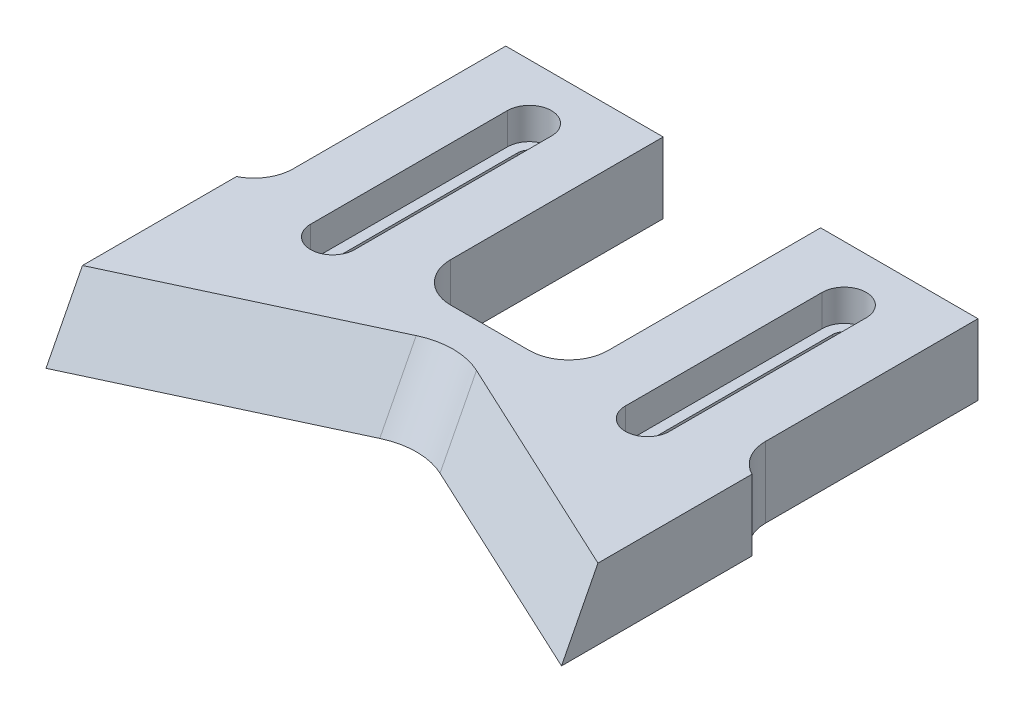
SolidWorks part; units mm, degrees
material "POM Acetal Copolymer"
ref_plane "Front Plane" through (0, 0, 0) normal (0, 0, 1) x (1, 0, 0)
ref_plane "Top Plane" through (0, 0, 0) normal (0, 1, 0) x (1, 0, 0)
ref_plane "Right Plane" through (0, 0, 0) normal (1, 0, 0) x (0, 0, -1)
sketch "Sketch1" plane through (0, 0, 0) normal (0, 1, 0) x (1, 0, 0)
  line L0 (0, 0) -> (0, 58)
  line L1 (0, 58) -> (75.5, 58)
  line L2 (75.5, 58) -> (75.5, 0)
  line L3 (75.5, 0) -> (37.75, 17.6031)
  line L4 (37.75, 17.6031) -> (0, 0)
  dimension "D1" = 58
  dimension "D2" = 65
  dimension "D3" = 75.5
extrude "Boss-Extrude1" add sketch "Sketch1" along normal blind 9
sketch "Sketch4" plane through (0, 9, 0) normal (0, 1, 0) x (1, 0, 0)
  line L0 (17.75, 51) -> (17.75, 26) construction
  line L1 (19.25, 51) -> (19.25, 26)
  line L2 (16.25, 51) -> (16.25, 26)
  line L3 (57.75, 51) -> (57.75, 26) construction
  line L4 (59.25, 51) -> (59.25, 26)
  line L5 (56.25, 51) -> (56.25, 26)
  line L6 (75.5, 58) -> (0, 58) construction
  line L9 (75.5, 58) -> (0, 58) construction
  arc A0 (19.25, 51) -> (16.25, 51) centre (17.75, 51) ccw
  arc A1 (16.25, 26) -> (19.25, 26) centre (17.75, 26) ccw
  arc A2 (59.25, 51) -> (56.25, 51) centre (57.75, 51) ccw
  arc A3 (56.25, 26) -> (59.25, 26) centre (57.75, 26) ccw
  point P2 (17.75, 38.5)
  point P7 (57.75, 38.5)
  point P14 (37.75, 58)
  dimension "D1" = 3
  dimension "D2" = 3
  dimension "D3" = 40
  dimension "D4" = 20
  dimension "D5" = 25
  dimension "D6" = 7
extrude "Cut-Extrude2" cut sketch "Sketch4" against normal up to next
sketch "Sketch5" plane through (0, 9, 0) normal (0, 1, 0) x (1, 0, 0)
  line L0 (75.5, 58) -> (0, 58) construction
  line L1 (27.75, 58) -> (47.75, 58)
  line L2 (27.75, 58) -> (27.75, 26)
  line L3 (27.75, 26) -> (47.75, 26)
  line L4 (47.75, 58) -> (47.75, 26)
  line L7 (67.75, 58) -> (75.5, 58)
  line L8 (0, 58) -> (7.75, 58)
  line L9 (0, 58) -> (0, 26)
  line L10 (0, 26) -> (7.75, 26)
  line L11 (7.75, 58) -> (7.75, 26)
  line L12 (67.75, 58) -> (67.75, 26)
  line L13 (67.75, 26) -> (75.5, 26)
  line L14 (75.5, 58) -> (75.5, 26)
  arc A0 (19.25, 51) -> (16.25, 51) centre (17.75, 51) ccw construction
  arc A1 (59.25, 51) -> (56.25, 51) centre (57.75, 51) ccw construction
  point P6 (17.75, 52.5)
  point P21 (57.75, 52.5)
  dimension "D1" = 20
  dimension "D2" = 20
  dimension "D3" = 32
  dimension "D4" = 10
  dimension "D5" = 10
extrude "Cut-Extrude3" cut sketch "Sketch5" against normal blind 10
fillet "Fillet1" radius 5 4 edges at (67.75, 4.5, -26) (47.75, 4.5, -26) (27.75, 4.5, -26) (7.75, 4.5, -26)
sketch "Sketch6" plane through (0, 9, 0) normal (0, 1, 0) x (1, 0, 0)
  line L0 (17.75, 51) -> (17.75, 26) construction
  line L1 (20.55, 51) -> (20.55, 26)
  line L2 (14.95, 51) -> (14.95, 26)
  line L3 (57.75, 51) -> (57.75, 26) construction
  line L4 (60.55, 51) -> (60.55, 26)
  line L5 (54.95, 51) -> (54.95, 26)
  arc A0 (20.55, 51) -> (14.95, 51) centre (17.75, 51) ccw
  arc A1 (14.95, 26) -> (20.55, 26) centre (17.75, 26) ccw
  arc A2 (60.55, 51) -> (54.95, 51) centre (57.75, 51) ccw
  arc A3 (54.95, 26) -> (60.55, 26) centre (57.75, 26) ccw
  point P4 (17.75, 38.5)
  point P9 (57.75, 38.5)
  dimension "D1" = 5.6
  dimension "D2" = 5.6
extrude "Cut-Extrude4" cut sketch "Sketch6" against normal blind 4
chamfer "Chamfer1" distance 9 angle 25 2 edges at (56.625, 9, -8.8016) (18.875, 9, -8.8016) first distance on face at (56.625, 4.5, -8.8016) first distance on face at (18.875, 4.5, -8.8016)
fillet "Fillet2" radius 10 1 edges at (37.75, 4.5, -19.9184)
sketch "Sketch7" plane through (0, 9, 0) normal (0, 1, 0) x (1, 0, 0)
  line L1 (0, 0) -> (5, 0)
  line L2 (0, 0) -> (0, 33.0851)
  line L3 (0, 33.0851) -> (5, 33.0851)
  line L4 (5, 0) -> (5, 33.0851)
  line L5 (75.5, 0) -> (70.5, 0)
  line L6 (75.5, 0) -> (75.5, 33.7453)
  line L7 (75.5, 33.7453) -> (70.5, 33.7453)
  line L8 (70.5, 0) -> (70.5, 33.7453)
  dimension "D1" = 5
extrude "Cut-Extrude5" cut sketch "Sketch7" against normal up to next
